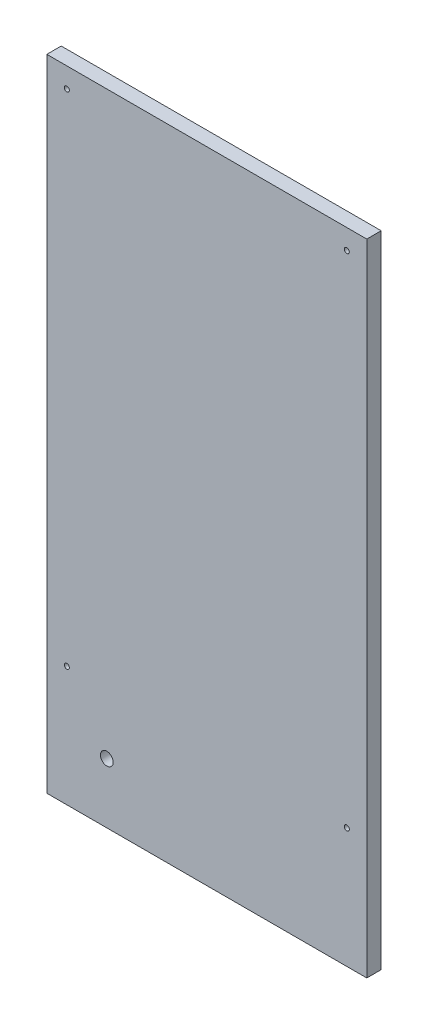
SolidWorks part; units mm, degrees
ref_plane "Front Plane" through (0, 0, 0) normal (0, 0, 1) x (1, 0, 0)
ref_plane "Top Plane" through (0, 0, 0) normal (0, 1, 0) x (1, 0, 0)
ref_plane "Right Plane" through (0, 0, 0) normal (1, 0, 0) x (0, 0, -1)
sketch "Sketch1" plane through (0, 0, 0) normal (0, 0, 1) x (1, 0, 0)
  line L1 (0, 0) -> (400, 0)
  line L2 (0, 0) -> (0, 800)
  line L3 (0, 800) -> (400, 800)
  line L4 (400, 0) -> (400, 800)
  dimension "D1" = 800
  dimension "D2" = 400
extrude "Base" add sketch "Sketch1" along normal blind 18
sketch "Sketch2" plane through (0, 0, 18) normal (0, 0, 1) x (1, 0, 0)
  line L0 (200, 800) -> (200, 0) construction
  line L1 (25, 775) -> (0, 775) construction
  line L2 (0, 800) -> (0, 0) construction
  line L3 (400, 800) -> (0, 800) construction
  line L4 (25, 775) -> (25, 800) construction
  line L5 (25, 800) -> (25, 0) construction
  line L6 (0, 0) -> (400, 0) construction
  line L8 (400, 400) -> (0, 400) construction
  line L9 (400, 0) -> (400, 800) construction
  line L10 (0, 800) -> (0, 0) construction
  circle A0 centre (25, 775) radius 3.15
  circle A1 centre (375, 775) radius 3.15
  circle A2 centre (25, 150) radius 3.15
  circle A3 centre (375, 150) radius 3.15
  dimension "D1" = 6.3
  dimension "D2" = 350
  dimension "D3" = 150
extrude "Mounting holes" cut sketch "Sketch2" against normal through all
sketch "Sketch3" [suppressed] plane through (0, 0, 0) normal (0, 0, -1) x (-1, 0, 0)
  line L0 (-400, 800) -> (0, 0) construction
  line L1 (-400, 0) -> (0, 800) construction
  line L2 (-400, 0) -> (-400, 800) construction
  line L3 (-350, 50) -> (-50, 50)
  line L4 (-350, 50) -> (-350, 750)
  line L5 (-350, 750) -> (-50, 750)
  line L6 (-50, 50) -> (-50, 750)
  line L7 (-350, 50) -> (-50, 750) construction
  line L8 (-350, 750) -> (-50, 50) construction
  line L9 (-350, 400) -> (-400, 400) construction
  line L10 (-200, 750) -> (-200, 800) construction
  line L11 (-400, 800) -> (0, 800) construction
  line L12 (-75, 50) -> (-75, 100) construction
  line L13 (-50, 50) -> (-350, 50)
  line L14 (-50, 50) -> (-50, 100)
  line L15 (-50, 100) -> (-350, 100)
  line L16 (-350, 50) -> (-350, 100)
  line L17 (-100, 75) -> (-50, 75) construction
  line L18 (-50, 50) -> (-100, 50)
  line L19 (-50, 50) -> (-50, 100)
  line L20 (-50, 100) -> (-100, 100)
  line L21 (-100, 50) -> (-100, 100)
  line L22 (-25, 775) -> (0, 775) construction
  line L23 (0, 800) -> (0, 0) construction
  line L24 (-25, 775) -> (-50, 775) construction
  line L25 (-50, 775) -> (-50, 800) construction
  line L26 (-400, 800) -> (0, 800) construction
  point P8 (-200, 400)
  point P29 (-75, 75)
extrude "Center hole" [suppressed] cut sketch "Sketch3" against normal up to next contours L15 L6 L5 L4 | L21 L13 L6 L15
sketch "Sketch4" plane through (0, 0, 0) normal (0, 0, -1) x (-1, 0, 0)
  line L0 (0, 0) -> (-400, 0) construction
  line L1 (0, 800) -> (-50, 800)
  line L2 (-400, 0) -> (-400, 800) construction
  line L3 (0, 800) -> (0, 0)
  line L4 (0, 0) -> (-400, 0)
  line L5 (0, 0) -> (0, 50)
  line L6 (0, 0) -> (-50, 0)
  line L7 (0, 50) -> (-400, 50)
  line L8 (-400, 0) -> (-400, 50)
  line L9 (-50, 800) -> (-50, 0)
  line L10 (-25, 0) -> (-25, 800) construction
  line L11 (-25, 775) -> (0, 775) construction
  line L12 (-200, 0) -> (-200, 50) construction
  line L14 (-75, 100) -> (-75, 50) construction
  line L15 (-50, 50) -> (-100, 50)
  line L16 (-50, 50) -> (-50, 100)
  line L17 (-50, 100) -> (-100, 100)
  line L18 (-100, 50) -> (-100, 100)
  line L19 (-100, 75) -> (-50, 75) construction
  line L20 (-50, 400) -> (0, 400) construction
  circle A0 centre (-75, 75) radius 8
  dimension "D1" = 16
extrude "Tap hole" cut sketch "Sketch4" against normal up to next contours A0 region at (75, 75, 0)
sketch "Sketch5" [suppressed] plane through (0, 0, 18) normal (0, 0, 1) x (1, 0, 0)
  circle A0 centre (25, 775) radius 7.2
  circle A1 centre (375, 775) radius 7.2
  circle A2 centre (375, 150) radius 7.2
  circle A3 centre (25, 150) radius 7.2
  dimension "D1" = 14.4
extrude "Mounting hole insets" [suppressed] cut sketch "Sketch5" against normal blind 2.15
sketch "Sketch6" plane through (0, 0, 18) normal (0, 0, 1) x (1, 0, 0)
  line L0 (25, 775) -> (0, 775) construction
  line L1 (0, 800) -> (0, 0) construction
  line L2 (25, 775) -> (50, 775) construction
  line L3 (50, 775) -> (50, 750) construction
  line L4 (0, 800) -> (400, 0) construction
  line L5 (400, 800) -> (0, 0) construction
  line L6 (50, 700) -> (350, 700)
  line L7 (350, 50) -> (50, 50)
  line L8 (350, 50) -> (350, 750)
  line L9 (350, 750) -> (50, 750)
  line L10 (50, 50) -> (50, 750)
  line L11 (350, 50) -> (50, 750) construction
  line L12 (350, 750) -> (50, 50) construction
  line L13 (50, 650) -> (350, 650)
  line L14 (50, 600) -> (350, 600)
  line L15 (50, 550) -> (350, 550)
  line L16 (50, 500) -> (350, 500)
  line L17 (50, 450) -> (350, 450)
  line L18 (50, 400) -> (350, 400)
  line L19 (50, 350) -> (350, 350)
  line L20 (50, 300) -> (350, 300)
  line L21 (50, 250) -> (350, 250)
  line L22 (50, 200) -> (350, 200)
  line L23 (50, 150) -> (350, 150)
  line L24 (50, 100) -> (350, 100)
  line L25 (200, 700) -> (200, 750) construction
  line L26 (200, 700) -> (200, 650) construction
  line L27 (100, 750) -> (100, 50)
  line L28 (100, 750) -> (50, 700) construction
  line L29 (150, 750) -> (150, 50)
  line L30 (100, 725) -> (50, 725) construction
  line L31 (200, 750) -> (200, 50)
  line L32 (250, 750) -> (250, 50)
  line L33 (300, 750) -> (300, 50)
  point P15 (200, 400)
  point P53 (75, 725)
  dimension "D1" = 50
  dimension "D2" = 13
  dimension "D3" = 5
equation "\"D2@Sketch2\"=\"GridSize\"*7"
equation "\"GridSize\"= 50"
equation "\"TapHoleSize\"=16"
equation "\"D1@Sketch4\"=\"TapHoleSize\""
equation "\"D1@Sketch6\"=\"GridSize\""
